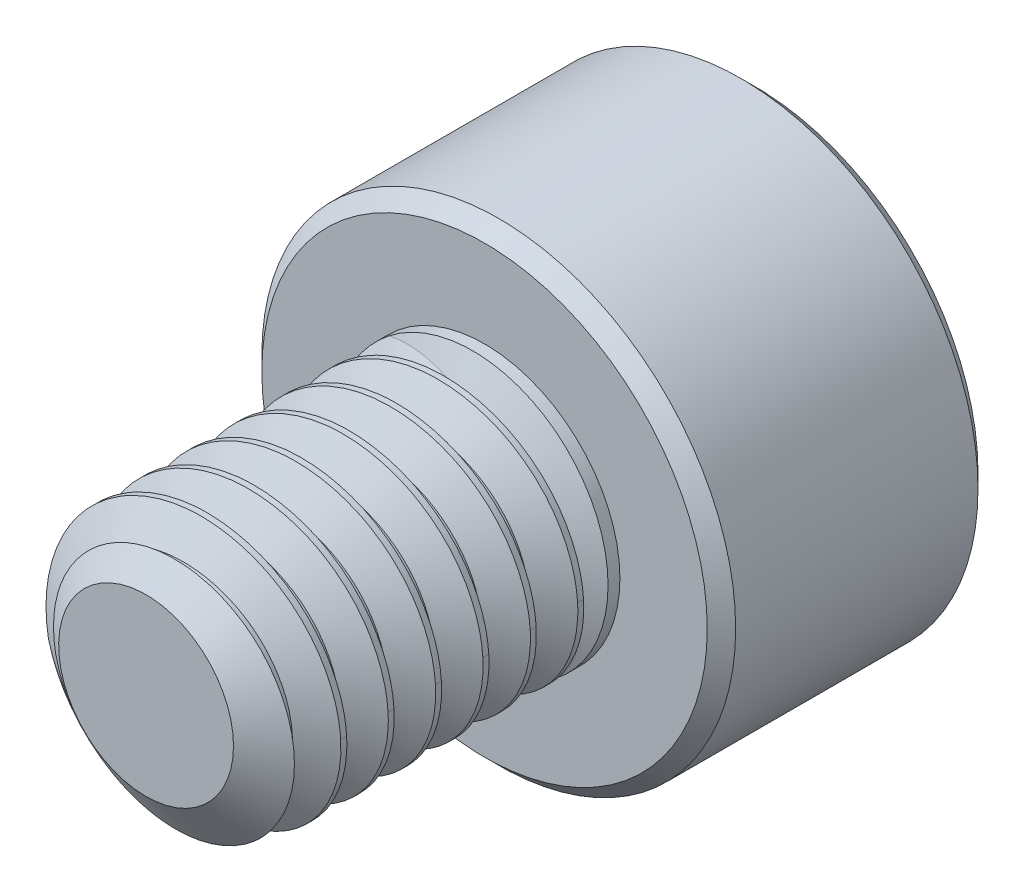
SolidWorks part; units mm, degrees
ref_plane "Front Plane" through (0, 0, 0) normal (0, 0, 1) x (1, 0, 0)
ref_plane "Top Plane" through (0, 0, 0) normal (0, 1, 0) x (1, 0, 0)
ref_plane "Right Plane" through (0, 0, 0) normal (1, 0, 0) x (0, 0, -1)
sketch "Sketch1" plane through (0, 0, 0) normal (0, 0, 1) x (1, 0, 0)
  circle A0 centre (0, 0) radius 2
  dimension "OD" = 4
extrude "Extrude1" add sketch "Sketch1" against normal blind 5
sketch "Sketch2" plane through (0, 0, 0) normal (0, 0, 1) x (1, 0, 0)
  circle A0 centre (0, 0) radius 2 construction
  circle A1 centre (0, 0) radius 2
curve "Helix/Spiral1" pitch 0.7 height 5.7 radius 2 centre (0, 0, 0) axis (0, 0, -1) start towards (0, 1, 0) parameters "pitch"=0.7
sketch "Sketch3" plane through (0, 0, 0) normal (1, 0, 0) x (0, 0, -1)
  line L0 (-0.6125, 2) -> (-0.35, 1.5453)
  line L1 (-0.35, 1.5453) -> (-0.2625, 1.5453)
  line L2 (-0.2625, 1.5453) -> (0, 2)
  line L3 (-0.6125, 2) -> (0, 2)
  line L4 (-0.3063, 2) -> (-0.3063, 1.5453) construction
  line L5 (-0.4813, 1.7727) -> (-0.1313, 1.7727) construction
  line L6 (0, 2) -> (0, -2) construction
  line L7 (0, -2) -> (5, -2) construction
  point P11 (3.15, -2)
  dimension "D1" = 0.0875
  dimension "D2" = 0.35
  dimension "D3" = 60
  dimension "D4" = 3.15
sweep "Cut-Sweep1" cut profiles "Sketch3" path "Helix/Spiral1" align with end faces yes
sketch "Sketch4" plane through (0, 0, 0) normal (1, 0, 0) x (0, 0, -1)
  line L0 (0.4962, 2) -> (0, 1.2913)
  line L1 (0, 1.2913) -> (0, 2)
  line L2 (0.4962, 2) -> (0, 2)
  line L3 (-0.6125, 2) -> (0, 2) construction
  line L4 (0, 0) -> (7.0209, 0) construction
  dimension "D1" = 55
  dimension "D2" = 0.254
revolve "Cut-Revolve1" cut sketch "Sketch4" angle 360 about L4
sketch "Sketch5" plane through (0, 0, 0) normal (1, 0, 0) x (0, 0, -1)
  line L0 (5, -0.9741) -> (5, 1.9864) construction
  line L1 (5, 2) -> (0.1203, 2)
  line L2 (5, 2) -> (5, 0)
  line L3 (5, 0) -> (0.0001, 0)
  line L4 (0.0001, 1.6698) -> (0.0001, 0)
  line L5 (0.1203, 2) -> (0.0001, 1.6698)
  line L6 (0, 0) -> (9.9695, 0) construction
  point P3 (0.0001, 2)
  point P10 (0.0001, 2)
  dimension "D1" = 0.3302
  dimension "Thread min" = 0.0001
  dimension "D3" = 20
revolve "partially thread" [suppressed] add sketch "Sketch5" angle 360 about L6
sketch "Sketch6" plane through (0, 0, -5) normal (0, 0, -1) x (-1, 0, 0)
  circle A0 centre (0, 0) radius 3.5
  dimension "head dia" = 7
extrude "Extrude2" add sketch "Sketch6" along normal blind 4
sketch "Sketch7" plane through (0, 0, -9) normal (0, 0, -1) x (-1, 0, 0)
  line L1 (0, 1.7321) -> (-1.5, 0.866)
  line L2 (-1.5, 0.866) -> (-1.5, -0.866)
  line L3 (-1.5, -0.866) -> (0, -1.7321)
  line L4 (0, -1.7321) -> (1.5, -0.866)
  line L5 (1.5, -0.866) -> (1.5, 0.866)
  line L6 (1.5, 0.866) -> (0, 1.7321)
  circle A0 centre (0, 0) radius 1.5 construction
  dimension "hex dia" = 3
extrude "Cut-Extrude1" cut sketch "Sketch7" against normal blind 2.25
sketch "Sketch8" plane through (0, 0, -9) normal (0, 0, -1) x (-1, 0, 0)
  circle A0 centre (0, 0) radius 1.7321
extrude "Cut-Extrude2" cut sketch "Sketch8" against normal through all draft 45
chamfer "Chamfer1" distance 0.21 angle 45 2 edges at (-3.5, 0, -9) (-3.5, 0, -5)
sketch "Sketch9" plane through (0, 0, 0) normal (1, 0, 0) x (0, 0, -1)
  line L0 (0, 2) -> (0, -2) construction
  line L1 (3.85, 2) -> (3.85, -2) construction
  dimension "D1" = 3.85
sketch "Sketch10" plane through (0, 0, 0) normal (1, 0, 0) x (0, 0, -1)
  line L0 (5, 2) -> (5, 0)
  line L1 (5, 2) -> (4.825, 2)
  line L2 (4.825, 2) -> (3.9966, 0)
  line L3 (5, 0) -> (3.9966, 0)
  line L4 (5, 3.29) -> (5, -3.29) construction
  dimension "D1" = 22.5
  dimension "D2" = 0.175
revolve "Revolve1" add sketch "Sketch10" angle 360 about L3
equation "\"D3@Helix/Spiral1\" = \"screw length@Extrude1\"+\"pitch@Helix/Spiral1\""
equation "\"D1@Sketch3\" = \"pitch@Helix/Spiral1\"*.125"
equation "\"D2@Sketch3\" = \"pitch@Helix/Spiral1\"*.5"
equation "\"D1@Cut-Extrude1\" = \"hex dia@Sketch7\"*.75"
equation "\"D1@Chamfer1\" = \"head dia@Sketch6\"*.03"
equation "\"D1@Sketch9\" = \"pitch@Helix/Spiral1\"*5.5"
equation "\"D2@Sketch10\" = \"pitch@Helix/Spiral1\"*.25"
equation "\"D4@Sketch3\" = \"pitch@Helix/Spiral1\"*4.50"
